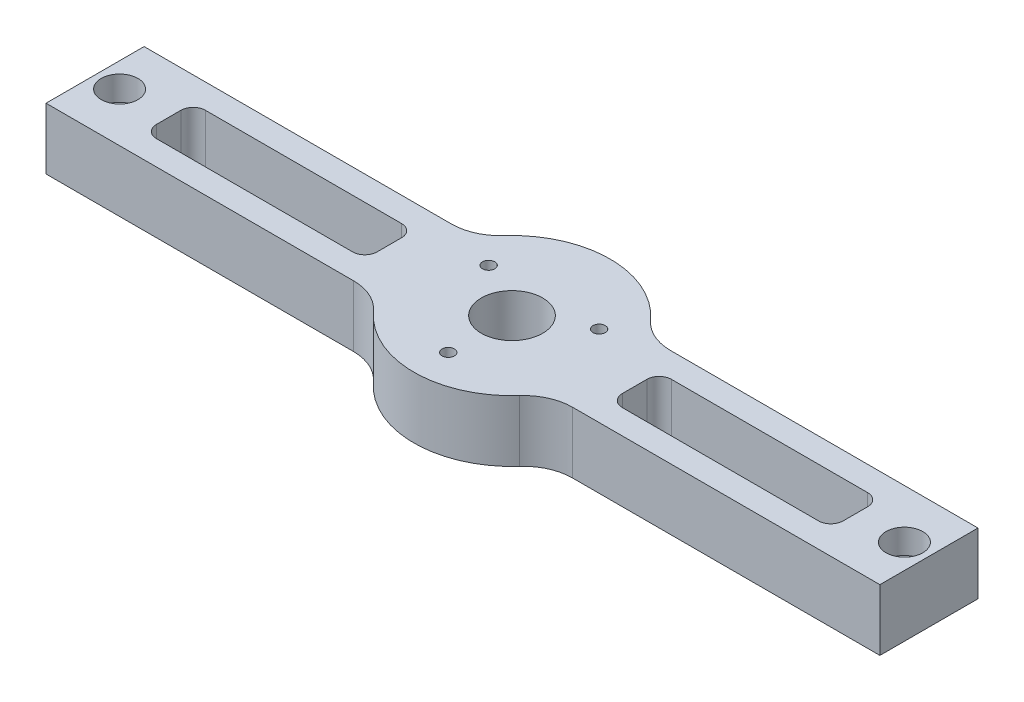
SolidWorks part; units mm, degrees
material "6061-T6 (SS)"
ref_plane "Front Plane" through (0, 0, 0) normal (0, 0, 1) x (1, 0, 0)
ref_plane "Top Plane" through (0, 0, 0) normal (0, 1, 0) x (1, 0, 0)
ref_plane "Right Plane" through (0, 0, 0) normal (1, 0, 0) x (0, 0, -1)
sketch "Sketch2" plane through (0, 0, 0) normal (0, 1, 0) x (1, 0, 0)
  line L0 (-21.997, 0) -> (0, 0) construction
  line L1 (-107.95, -25.4) -> (-21.997, -25.4)
  line L2 (-107.95, -25.4) -> (-107.95, 0)
  line L3 (-107.95, 0) -> (-21.997, 0)
  line L4 (-21.997, -25.4) -> (-21.997, 0)
  line L5 (21.997, -25.4) -> (107.95, -25.4)
  line L6 (21.997, -25.4) -> (21.997, 0)
  line L7 (21.997, 0) -> (107.95, 0)
  line L8 (107.95, -25.4) -> (107.95, 0)
  line L9 (0, 0) -> (21.997, 0) construction
  circle A0 centre (0, -12.7) radius 7.9375
  circle A1 centre (0, -12.7) radius 25.4
  point P13 (107.95, -12.7)
  dimension "D3" = 215.9
  dimension "D4" = 15.875
  dimension "D5" = 50.8
  dimension "D1" = 25.4
  dimension "D2" = 25.4
extrude "Boss-Extrude1" add sketch "Sketch2" along normal blind 15.875 contours A1 L3 L2 L1 | L4 A1 | L6 A1 L4 A0 | L6 A1 | A1 L5 L8 L7 region at (-66.1179, 0, 12.7) region at (-23.3664, 0, 12.7) region at (-21.325, 0, 12.7) region at (66.1179, 0, 12.7) region at (23.3664, 0, 12.7)
fillet "Fillet1" radius 12.7 4 edges at (21.997, 7.9375, 0) (21.997, 7.9375, 25.4) (-21.997, 7.9375, 25.4) (-21.997, 7.9375, 0)
sketch "Sketch3" plane through (0, 0, 0) normal (0, -1, 0) x (1, 0, 0)
  circle A0 centre (0, 12.7) radius 22.225
  dimension "D1" = 44.45
extrude "Cut-Extrude1" cut sketch "Sketch3" against normal blind 3.175
sketch "Sketch4" plane through (0, 15.875, 0) normal (0, 1, 0) x (1, 0, 0)
  line L0 (-107.95, -25.4) -> (-107.95, 0) construction
  line L1 (107.95, -25.4) -> (107.95, 0) construction
  circle A0 centre (-101.6, -12.7) radius 4.7625
  circle A1 centre (101.6, -12.7) radius 4.7625
  point P4 (-107.95, -12.7)
  point P5 (107.95, -12.7)
  dimension "D1" = 9.525
  dimension "D2" = 9.525
  dimension "D3" = 6.35
  dimension "D4" = 6.35
extrude "Cut-Extrude2" cut sketch "Sketch4" against normal blind 6.35
sketch "Sketch5" plane through (0, 9.525, 0) normal (0, 1, 0) x (1, 0, 0)
  circle A0 centre (-101.6, -12.7) radius 3.175
  circle A1 centre (101.6, -12.7) radius 3.175
  dimension "D1" = 6.35
  dimension "D2" = 6.35
extrude "Cut-Extrude3" cut sketch "Sketch5" against normal through all
sketch "Sketch6" plane through (0, 3.175, 0) normal (0, -1, 0) x (1, 0, 0)
  circle A0 centre (0, 29.21) radius 1.5875
  circle A1 centre (0, 12.7) radius 7.9375 construction
  circle A2 centre (0, 12.7) radius 7.9375 construction
  circle A3 centre (14.2981, 4.445) radius 1.5875
  circle A4 centre (-14.2981, 4.445) radius 1.5875
  dimension "D2" = 3.175
  dimension "D1" = 16.51
  dimension "D3" = 3
extrude "Cut-Extrude4" cut sketch "Sketch6" against normal through all
sketch "Sketch7" plane through (0, 15.875, 0) normal (0, 1, 0) x (1, 0, 0)
  line L0 (-107.95, 0) -> (-28.3981, 0) construction
  line L1 (-88.9, -19.05) -> (-31.75, -19.05)
  line L2 (-88.9, -19.05) -> (-88.9, -6.35)
  line L3 (-88.9, -6.35) -> (-31.75, -6.35)
  line L4 (-31.75, -19.05) -> (-31.75, -6.35)
  line L5 (31.75, -19.05) -> (88.9, -19.05)
  line L6 (31.75, -19.05) -> (31.75, -6.35)
  line L7 (31.75, -6.35) -> (88.9, -6.35)
  line L8 (88.9, -19.05) -> (88.9, -6.35)
  line L9 (-107.95, -25.4) -> (-28.3981, -25.4) construction
  circle A0 centre (-101.6, -12.7) radius 4.7625 construction
  circle A1 centre (101.6, -12.7) radius 4.7625 construction
  dimension "D3" = 12.7
  dimension "D1" = 6.35
  dimension "D2" = 6.35
  dimension "D4" = 63.5
  dimension "D5" = 12.7
extrude "Cut-Extrude5" cut sketch "Sketch7" against normal through all
fillet "Fillet2" radius 3.175 8 edges at (31.75, 7.9375, 6.35) (31.75, 7.9375, 19.05) (88.9, 7.9375, 19.05) (88.9, 7.9375, 6.35) (-31.75, 7.9375, 6.35) (-31.75, 7.9375, 19.05) (-88.9, 7.9375, 19.05) (-88.9, 7.9375, 6.35)
